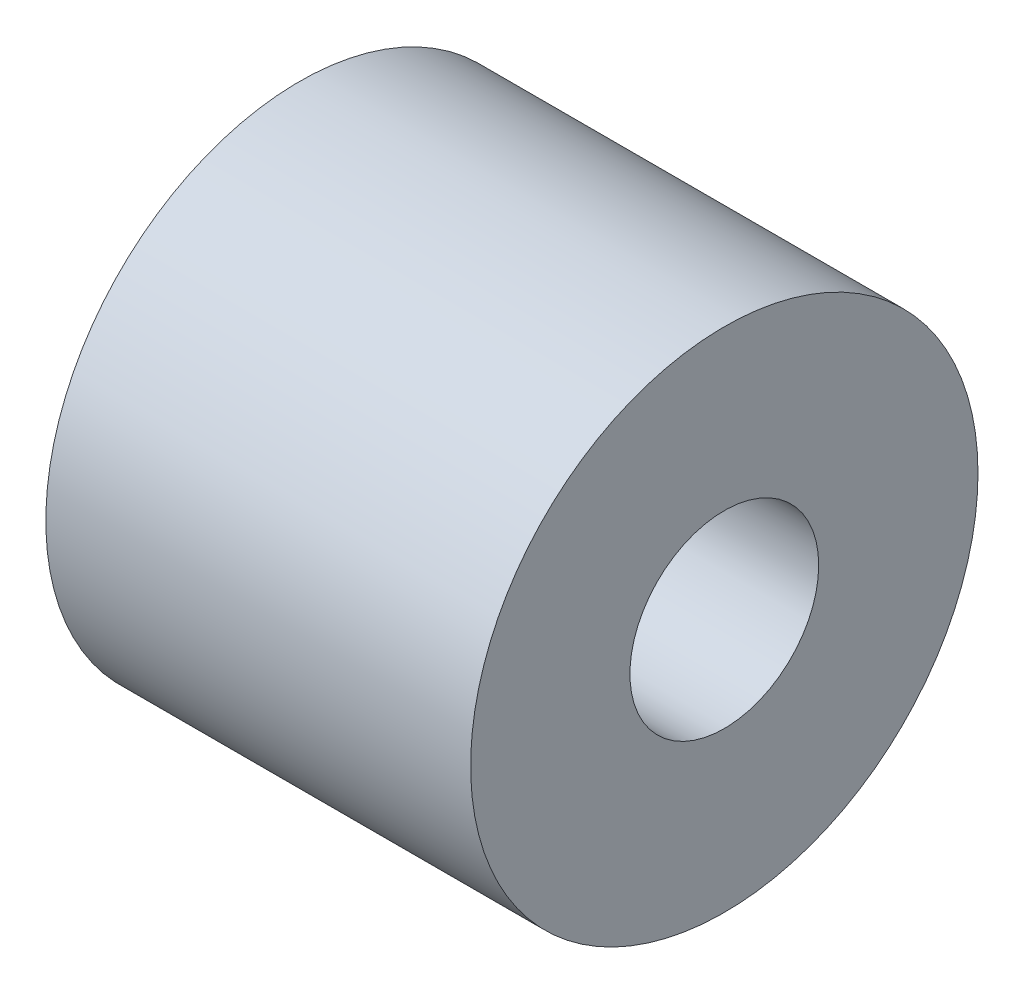
SolidWorks part; units mm, degrees
ref_plane "Front" through (0, 0, 0) normal (0, 0, 1) x (1, 0, 0)
ref_plane "Top" through (0, 0, 0) normal (0, 1, 0) x (1, 0, 0)
ref_plane "Right" through (0, 0, 0) normal (1, 0, 0) x (0, 0, -1)
sketch "Sketch1" plane through (0, 0, 0) normal (1, 0, 0) x (0, 0, -1)
  circle A0 centre (0, 0) radius 10.75
  circle A1 centre (0, 0) radius 4
  dimension "D1" = 21.5
  dimension "D2" = 8
extrude "Boss-Extrude1" add sketch "Sketch1" along normal blind 18
